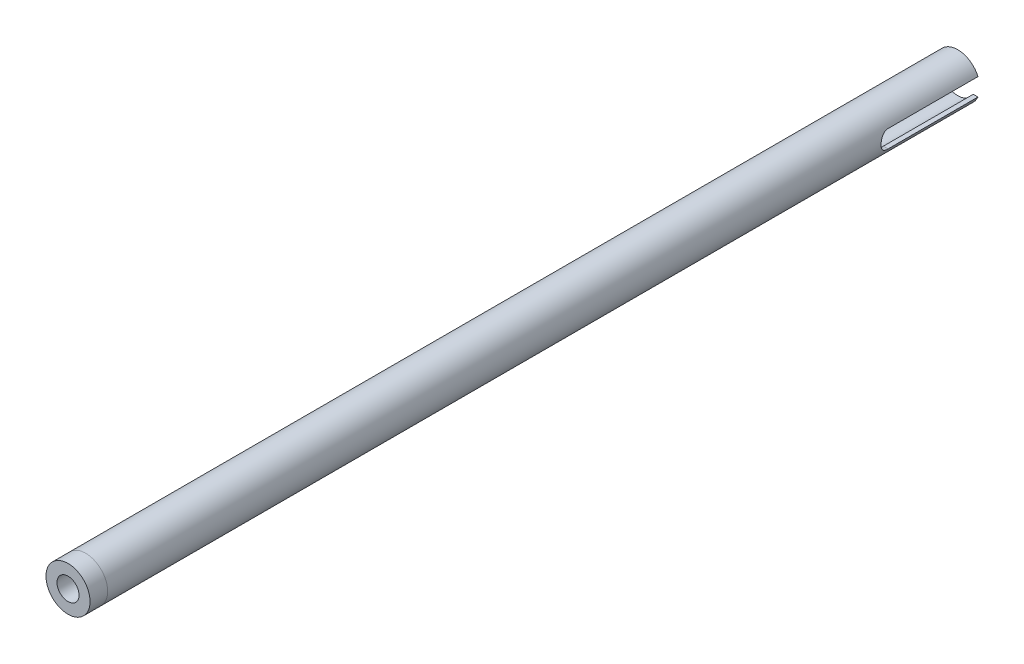
SolidWorks part; units mm, degrees
material "AISI 4130 Steel, annealed at 865C"
ref_plane "Front Plane" through (0, 0, 0) normal (0, 0, 1) x (1, 0, 0)
ref_plane "Top Plane" through (0, 0, 0) normal (0, 1, 0) x (1, 0, 0)
ref_plane "Right Plane" through (0, 0, 0) normal (1, 0, 0) x (0, 0, -1)
sketch "Axis" plane through (0, 0, 0) normal (0, 1, 0) x (1, 0, 0)
  line L0 (0, 0) -> (0, 320.3418) construction
  line L1 (0, 0) -> (0, -34.925) construction
  line L2 (0, 320.3418) -> (-7.9375, 320.3418) construction
  line L3 (0, 349.3139) -> (-25.9801, 254.4858) construction
  dimension "D1" = 34.925
  dimension "D2" = 7.9375
sketch "Sketch1" plane through (0, 0, 0) normal (0, 0, 1) x (1, 0, 0)
  line L0 (-7.9375, 0) -> (7.9375, 0) construction
  line L1 (-7.2748, 3.175) -> (7.2748, 3.175)
  line L2 (-7.2748, -3.175) -> (7.2748, -3.175)
  circle A0 centre (0, 0) radius 7.9375
  circle A1 centre (0, 0) radius 6.4135
  circle A2 centre (0, 0) radius 3.9688
  dimension "D1" = 15.875
  dimension "D3" = 7.9375
  dimension "D2" = 1.524
  dimension "D4" = 6.35
extrude "Threaded insert 1-1" add sketch "Sketch1" against normal blind 6.35 contours A2 L1 A1 | A1 L1 A0 | A2 L0 A1 L1 | A1 L0 A0 L1 | L0 A1 L2 A0 | L0 A2 L2 A1 | A2 L2 A1 | A1 L2 A0 | L0 A1 L2 A2 | L0 A0 L2 A1 | A0 L0 A1 L1 | A1 L0 A2 L1 region at (4.7887, 1.6543, 0) region at (4.7887, -1.6543, 0) region at (6.9234, 1.6163, 0) region at (6.9234, -1.6163, 0) region at (-4.7887, -1.6543, 0) region at (-4.7887, 1.6543, 0) region at (0, 4.6159, 0) region at (0, -4.6159, 0) region at (0, 6.5666, 0) region at (6.4237, -3.3281, 0) region at (-6.9234, -1.6163, 0) region at (-6.9234, 1.6163, 0)
extrude "Threaded insert 1-2" add sketch "Sketch1<3>" against normal blind 9.525 from surface contours A2 L1 A1 | A2 L0 A1 L1 | L0 A2 L2 A1 | A2 L2 A1 | L0 A1 L2 A2 | A1 L0 A2 L1 region at (4.7887, 1.6543, 0) region at (4.7887, -1.6543, 0) region at (-4.7887, -1.6543, 0) region at (-4.7887, 1.6543, 0) region at (0, 4.6159, 0) region at (0, -4.6159, 0) starting at face at (7.9375, 0, -6.35)
sketch "Sketch1<3>" plane through (0, 0, 0) normal (0, 0, 1) x (1, 0, 0) same geometry as "Sketch1"
extrude "A-arm tube" add sketch "Sketch1<4>" against normal up to vertex (320.3418 mm away) from surface separate body contours A1 L1 A0 | A1 L0 A0 L1 | L0 A1 L2 A0 | A1 L2 A0 | L0 A0 L2 A1 | A0 L0 A1 L1 region at (6.9234, 1.6163, 0) region at (6.9234, -1.6163, 0) region at (0, 6.5666, 0) region at (6.4237, -3.3281, 0) region at (-6.9234, -1.6163, 0) region at (-6.9234, 1.6163, 0) up to point (0, 0, -320.3418) starting at face at (6.4135, 0, -6.35)
sketch "Sketch1<4>" plane through (0, 0, 0) normal (0, 0, 1) x (1, 0, 0) same geometry as "Sketch1"
extrude "Apex slot" cut sketch "Sketch1<5>" along normal blind 35.56 from surface contours A0 L0 A1 L1 | L0 A0 L2 A1 | A1 L0 A0 L1 | L0 A1 L2 A0 region at (6.9234, 1.6163, 0) region at (6.9234, -1.6163, 0) region at (-6.9234, -1.6163, 0) region at (-6.9234, 1.6163, 0) starting at face at (6.4135, 0, -320.3418)
sketch "Sketch1<5>" plane through (0, 0, 0) normal (0, 0, 1) x (1, 0, 0) same geometry as "Sketch1"
fillet "Fillet1" radius 3.175 4 edges at (-6.4237, 3.175, -284.7818) (-6.4237, -3.175, -284.7818) (6.4237, -3.175, -284.7818) (6.4237, 3.175, -284.7818)
equation "\"tube diameter\"= 5 / 8"
equation "\"tube thickness\"= .06"
equation "\"apex thickness\"= .25"
equation "\"tube slot\"= 1.4"
equation "\"D1@Sketch1\"=\"tube diameter\""
equation "\"D2@Sketch1\"=\"tube thickness\""
equation "\"threaded insert hole\"= .3125"
equation "\"D3@Sketch1\"=\"threaded insert hole\""
equation "\"D4@Sketch1\"=\"apex thickness\""
equation "\"D1@Apex slot\" = \"tube slot\""
equation "\"D1@Fillet1\"=\"apex thickness\"/2"
